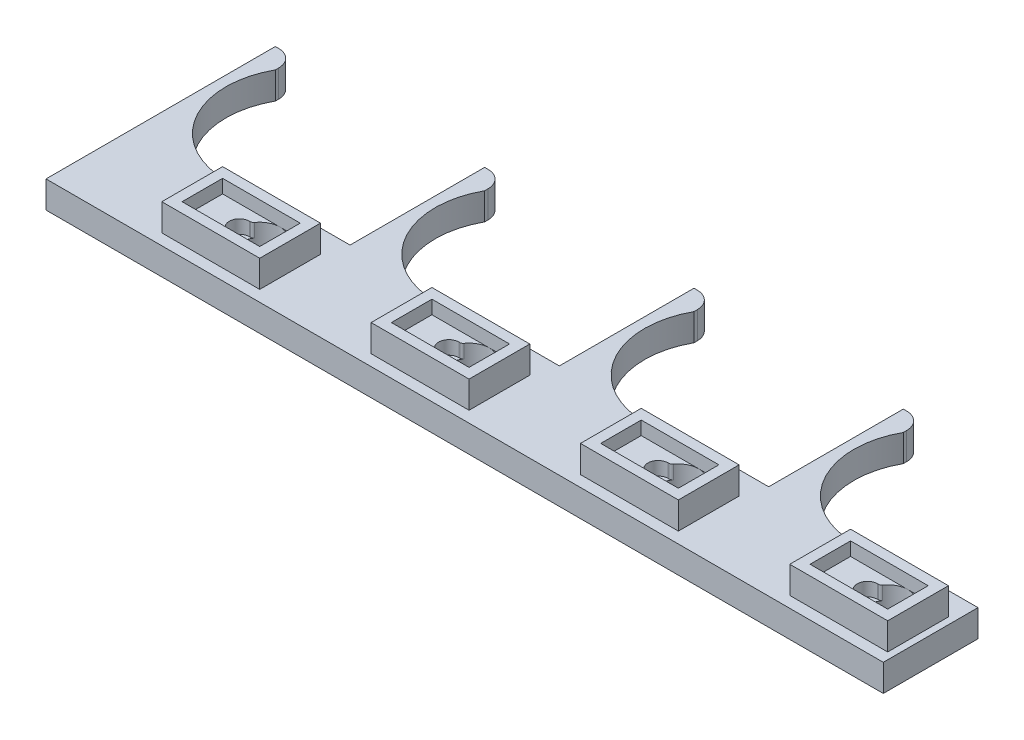
SolidWorks part; units mm, degrees
ref_plane "Plan de face" through (0, 0, 0) normal (0, 0, 1) x (1, 0, 0)
ref_plane "Plan de dessus" through (0, 0, 0) normal (0, 1, 0) x (1, 0, 0)
ref_plane "Plan de droite" through (0, 0, 0) normal (1, 0, 0) x (0, 0, -1)
sketch "Esquisse1" plane through (0, 0, 0) normal (0, 1, 0) x (1, 0, 0)
  line L1 (0, 0) -> (6, 0)
  line L2 (0, 0) -> (0, 67.9235)
  line L3 (0, 67.9235) -> (1, 67.9235)
  line L4 (6, 0) -> (6, 67.9235) construction
  line L5 (36, 0) -> (6, 0)
  line L6 (6, 61.9235) -> (6, 62.9235)
  line L7 (52, 50.3046) -> (52, 0) construction
  line L8 (36, 28.056) -> (62, 28.056)
  line L10 (36, 0) -> (62, 0)
  line L11 (62, 28.056) -> (62, 0)
  line L12 (36, 28.056) -> (36, 0) construction
  line L13 (52, 12.3046) -> (51, 12.3046) construction
  arc A0 (6, 61.9235) -> (36, 28.056) centre (27, 50.3046) ccw
  circle A1 centre (27, 50.3046) radius 25 construction
  arc A2 (1, 67.9235) -> (6, 62.9235) centre (1, 62.9235) cw
  circle A3 centre (51, 12.3046) radius 6
  dimension "D1" = 24
  dimension "D3" = 50
  dimension "D7" = 5
  dimension "D9" = 12
  dimension "D2" = 21
  dimension "D4" = 30
  dimension "D5" = 6
  dimension "D6" = 6
  dimension "D8" = 1
  dimension "D10" = 38
  dimension "D11" = 62
extrude "Boss.-Extru.1" add sketch "Esquisse1" along normal blind 8
sketch "Esquisse2" plane through (0, 8, 0) normal (0, 1, 0) x (1, 0, 0)
  line L0 (51, 12.3046) -> (45, 12.3046) construction
  line L1 (45, 15.3046) -> (45.2554, 15.3046)
  line L2 (45, 9.3046) -> (45.2554, 9.3046)
  line L8 (31, 21.3046) -> (60, 21.3046)
  line L9 (31, 21.3046) -> (31, 3.3046)
  line L10 (31, 3.3046) -> (60, 3.3046)
  line L11 (60, 21.3046) -> (60, 3.3046)
  circle A0 centre (51, 12.3046) radius 6 construction
  circle A1 centre (45, 12.3046) radius 3 construction
  arc A2 (46.0761, 15.7332) -> (46.0761, 8.876) centre (51, 12.3046) cw
  arc A3 (45, 15.3046) -> (45, 9.3046) centre (45, 12.3046) ccw
  arc A4 (45.2554, 9.3046) -> (46.0761, 8.876) centre (45.2554, 8.3046) cw
  arc A5 (45.2554, 15.3046) -> (46.0761, 15.7332) centre (45.2554, 16.3046) ccw
  point P15 (45.8038, 9.3046)
  point P18 (45.8038, 15.3046)
  point P27 (60, 12.3046)
  dimension "D1" = 12
  dimension "D2" = 6
  dimension "D4" = 1
  dimension "D3" = 6
  dimension "D5" = 9
  dimension "D7" = 18
  dimension "D8" = 29
extrude "Boss.-Extru.2" add sketch "Esquisse2" along normal blind 4 contours L9 L8 L11 L10 | A3 L2 A4 A2 A5 L1
sketch "Esquisse3" plane through (0, 12, 0) normal (0, 1, 0) x (1, 0, 0)
  line L1 (34, 18.3046) -> (57, 18.3046)
  line L2 (34, 18.3046) -> (34, 6.3046)
  line L3 (34, 6.3046) -> (57, 6.3046)
  line L4 (57, 18.3046) -> (57, 6.3046)
  line L5 (31, 21.3046) -> (60, 21.3046)
  line L6 (31, 21.3046) -> (31, 3.3046)
  line L7 (31, 3.3046) -> (60, 3.3046)
  line L8 (60, 21.3046) -> (60, 3.3046)
  arc A0 (46.0761, 8.876) -> (46.0761, 15.7332) centre (51, 12.3046) ccw construction
  dimension "D1" = 12
  dimension "D2" = 23
extrude "Boss.-Extru.3" add sketch "Esquisse3" along normal blind 4
sketch "Esquisse4" plane through (0, 0, 0) normal (0, -1, 0) x (1, 0, 0)
  line L0 (62, -28.056) -> (36, -28.056) construction
  line L1 (47.7, -17.056) -> (54.3, -17.056)
  line L3 (47.7, -28.056) -> (54.3, -28.056)
  line L5 (51, -12.3046) -> (51, -17.056) construction
  line L6 (51, -12.3046) -> (52.0099, -17.056) construction
  line L7 (55.1937, -16.1623) -> (57.7218, -28.056)
  line L8 (54.3, -17.056) -> (55.1937, -16.1623)
  line L9 (54.3, -28.056) -> (57.7218, -28.056)
  line L10 (54.3, -17.056) -> (54.3, -28.056) construction
  line L11 (46.8063, -16.1623) -> (44.2782, -28.056)
  line L12 (46.8063, -16.1623) -> (47.7, -17.056)
  line L13 (47.7, -17.056) -> (47.7, -28.056) construction
  line L14 (44.2782, -28.056) -> (47.7, -28.056)
  point P12 (51, -17.056)
  dimension "D1" = 12
  dimension "D2" = 3.3
  dimension "D3" = 6.6
  dimension "D4" = 11
  dimension "D5" = 135
extrude "Enlèv. mat.-Extru.1" cut sketch "Esquisse4" against normal blind 4
pattern_linear "Répétition linéaire1" count 4 spacing 62 along (1, 0, 0) of "Boss.-Extru.1", "Boss.-Extru.3", "Boss.-Extru.2", "Enlèv. mat.-Extru.1"
